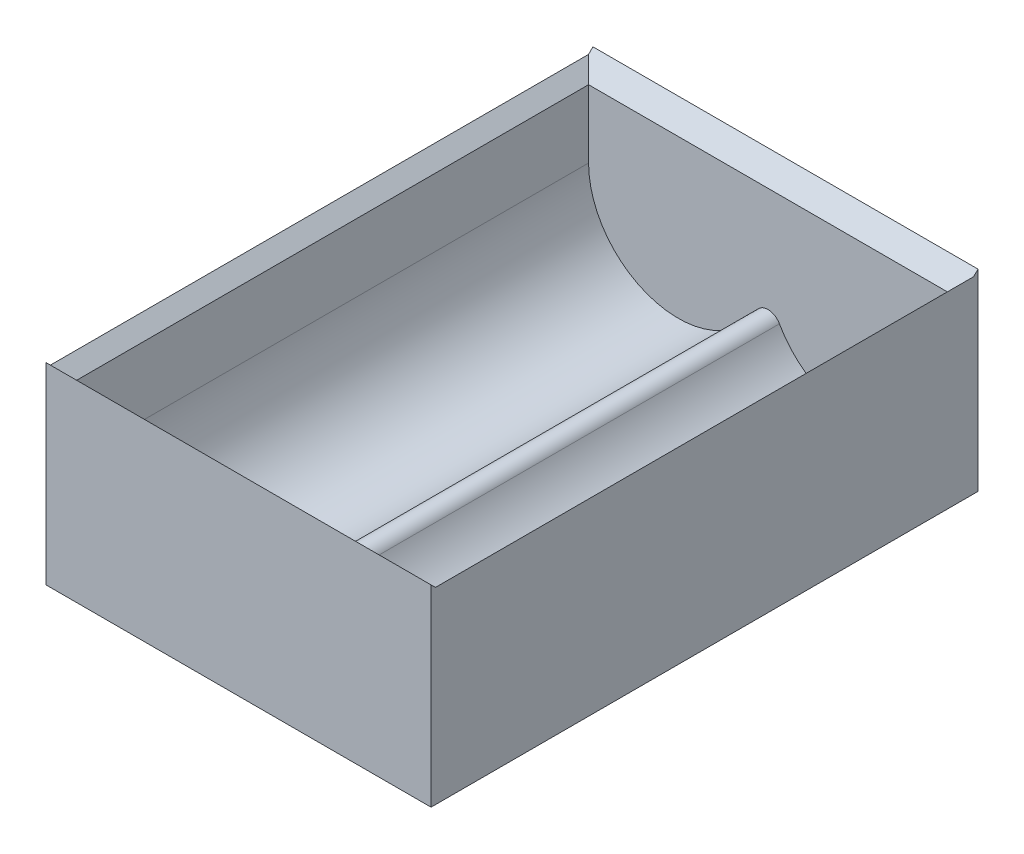
SolidWorks part; units mm, degrees
ref_plane "Front Plane" through (0, 0, 0) normal (0, 0, 1) x (1, 0, 0)
ref_plane "Top Plane" through (0, 0, 0) normal (0, 1, 0) x (1, 0, 0)
ref_plane "Right Plane" through (0, 0, 0) normal (1, 0, 0) x (0, 0, -1)
sketch "Sketch1" plane through (0, 0, 0) normal (0, 1, 0) x (1, 0, 0)
  line L1 (-44, 62.5) -> (44, 62.5)
  line L2 (-44, 62.5) -> (-44, -62.5)
  line L3 (-44, -62.5) -> (44, -62.5)
  line L4 (44, 62.5) -> (44, -62.5)
  line L5 (-44, 62.5) -> (44, -62.5) construction
  line L6 (-44, -62.5) -> (44, 62.5) construction
  point P0 (0, 0)
  dimension "D1" = 125
  dimension "D2" = 88
extrude "Boss-Extrude1" add sketch "Sketch1" along normal blind 50
ref_plane "Plane1" through (0, 0, 58.5) normal (0, 0, 1) x (1, 0, 0)
sketch "Sketch2" plane through (0, 0, 58.5) normal (0, 0, 1) x (1, 0, 0)
  line L1 (0, 0) -> (0, 33.8796) construction
  line L5 (-44, 0) -> (44, 0) construction
  line L6 (-44, 50) -> (-44, 0) construction
  line L7 (-41, 24.5) -> (-41, 66.5)
  line L8 (-41, 66.5) -> (41, 66.5)
  line L9 (41, 24.5) -> (41, 66.5)
  arc A2 (-41, 24.5) -> (0, 24.5) centre (-20.5, 24.5) ccw
  arc A3 (41, 24.5) -> (0, 24.5) centre (20.5, 24.5) cw
  point P13 (0, 66.5)
  dimension "D1" = 24.5
  dimension "D2" = 20.5
  dimension "D3" = 3
  dimension "D4" = 42
extrude "Cut-Extrude1" cut sketch "Sketch2" against normal offset from surface (117 mm away) 4 contours A3 L9 L8 L7 A2 region at (0, 37.2695, 58.5) up to face at (0, 25, -62.5)
fillet "Fillet1" radius 3 1 edges at (0, 24.5, 0)
chamfer "Chamfer1" distance 10 angle 45 4 edges at (0, 50, 58.5) (41, 50, 0) (-41, 50, 0) (0, 50, -58.5)
